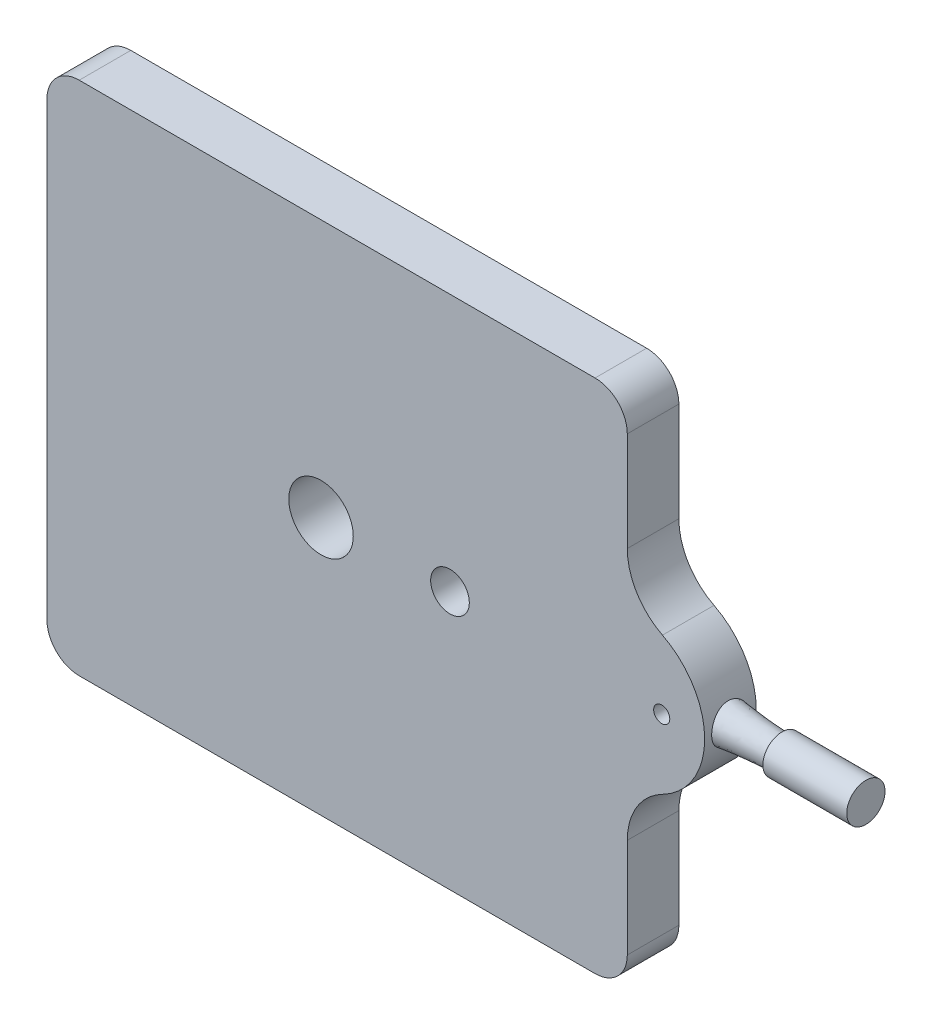
SolidWorks part; units mm, degrees
material "ASTM A36 Steel"
ref_plane "Front Plane" through (0, 0, 0) normal (0, 0, 1) x (1, 0, 0)
ref_plane "Top Plane" through (0, 0, 0) normal (0, 1, 0) x (1, 0, 0)
ref_plane "Right Plane" through (0, 0, 0) normal (1, 0, 0) x (0, 0, -1)
sketch "Sketch1" plane through (0, 0, 0) normal (0, 0, 1) x (1, 0, 0)
  line L0 (0, 25.4041) -> (0, 80)
  line L1 (0, 0) -> (90, 0)
  line L2 (0, 0) -> (0, 25.4041)
  line L3 (0, 80) -> (90, 80)
  line L4 (90, 0) -> (90, 20.4041)
  line L5 (90, 59.5959) -> (90, 80)
  line L6 (-16.1419, 40) -> (83.8007, 40) construction
  arc A0 (95.4545, 50.6887) -> (95.4545, 29.3113) centre (90, 40) cw
  circle A1 centre (42.5, 40) radius 5
  arc A2 (95.4545, 29.3113) -> (90, 20.4041) centre (100, 20.4041) ccw
  arc A3 (95.4545, 50.6887) -> (90, 59.5959) centre (100, 59.5959) cw
  point P12 (0, 57)
  point P16 (90, 52)
  dimension "D3" = 10
  dimension "D4" = 42.5
  dimension "D1" = 80
  dimension "D2" = 90
extrude "Boss-Extrude1" add sketch "Sketch1" along normal blind 8
ref_plane "Plane1" through (98, 0, 0) normal (1, 0, 0) x (0, 0, -1)
sketch "Sketch2" plane through (98, 0, 0) normal (1, 0, 0) x (0, 0, -1)
  circle A0 centre (-4, 40) radius 3.4718
ref_plane "Plane2" through (113, 0, 0) normal (1, 0, 0) x (0, 0, -1)
sketch "Sketch3" plane through (113, 0, 0) normal (1, 0, 0) x (0, 0, -1)
  circle A0 centre (-4, 40) radius 2.3304
loft "Loft1" add profiles "Sketch2", "Sketch3" connector at (98, 43.2576, 2.7994) connector at (113, 40.4295, 1.7095)
sketch "Sketch4" plane through (113, 0, 0) normal (1, 0, 0) x (0, 0, -1)
  circle A0 centre (-4, 40) radius 2.97
extrude "Boss-Extrude2" add sketch "Sketch4" along normal blind 10 and the other way blind 3
fillet "Fillet6" radius 5 4 edges at (90, 80, 4) (0, 80, 4) (0, 0, 4) (90, 0, 4)
sketch "Sketch5" plane through (0, 0, 8) normal (0, 0, 1) x (1, 0, 0)
  line L0 (0, 75) -> (0, 5) construction
  line L1 (5, 0) -> (85, 0) construction
  circle A1 centre (95.34, 40) radius 1.25
  point P0 (95.34, 40)
  dimension "D2" = 40
  dimension "D1" = 95.34
extrude "Cut-Extrude2" cut sketch "Sketch5" against normal blind 10
sketch "Sketch6" plane through (0, 0, 8) normal (0, 0, 1) x (1, 0, 0)
  circle A0 centre (62.5, 40.063) radius 3
  circle A1 centre (42.5, 40) radius 5 construction
  dimension "D1" = 20
extrude "Cut-Extrude3" cut sketch "Sketch6" against normal blind 10
